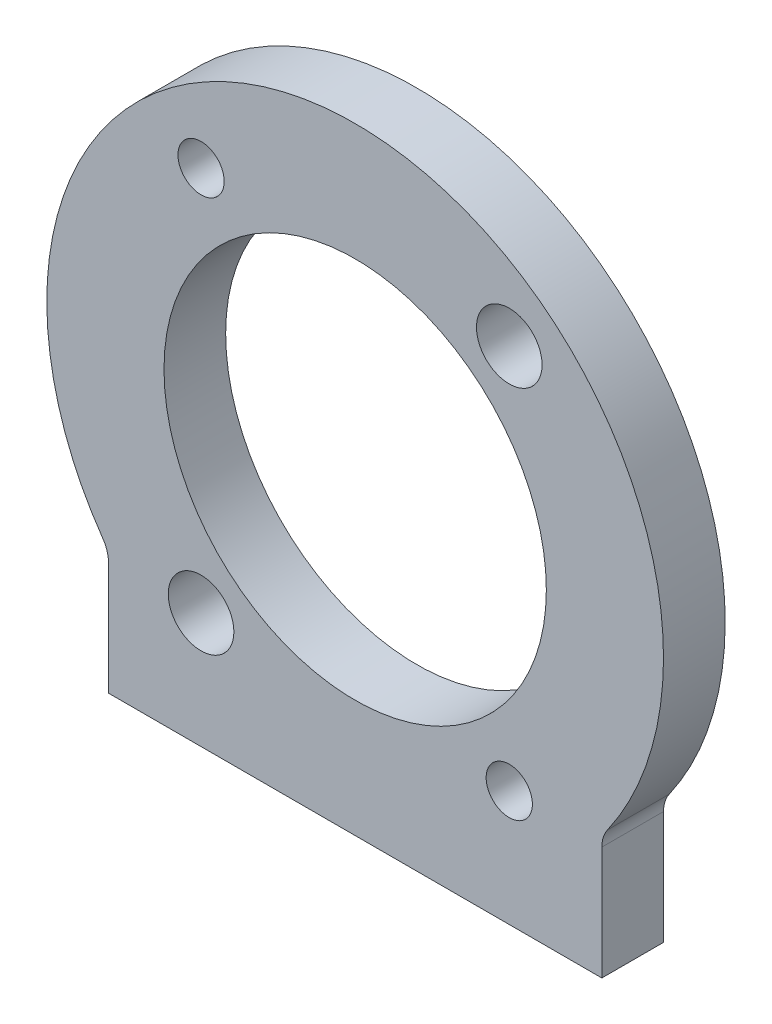
SolidWorks part; units mm, degrees
material "6061 Alloy"
ref_plane "Front" through (0, 0, 0) normal (0, 0, 1) x (1, 0, 0)
ref_plane "Top" through (0, 0, 0) normal (0, 1, 0) x (1, 0, 0)
ref_plane "Right" through (0, 0, 0) normal (1, 0, 0) x (0, 0, -1)
sketch "Sketch1" plane through (0, 0, 0) normal (0, 0, 1) x (1, 0, 0)
  line L0 (-50.8, 63.5) -> (0, 0) construction
  line L1 (0, 0) -> (-50.8, 0)
  line L2 (0, 0) -> (0, 11.6695)
  line L3 (0, 63.5) -> (-50.8, 63.5) construction
  line L4 (-50.8, 0) -> (-50.8, 11.6695)
  line L5 (0, 63.5) -> (-50.8, 0) construction
  line L6 (0, 50.8) -> (0, 63.5) construction
  line L7 (-50.8, 50.8) -> (-50.8, 63.5) construction
  circle A0 centre (-25.4, 31.75) radius 19.685
  circle A2 centre (-25.4, 31.75) radius 25.4 construction
  circle A4 centre (-41.2673, 51.5841) radius 2.3812
  circle A5 centre (-9.5327, 51.5841) radius 3.3782
  circle A6 centre (-9.5327, 11.9159) radius 2.3813
  circle A7 centre (-41.2673, 11.9159) radius 3.3782
  arc A9 (0.5773, 13.495) -> (-51.3773, 13.495) centre (-25.4, 31.75) ccw
  arc A10 (0, 11.6695) -> (0.5773, 13.495) centre (3.175, 11.6695) cw
  arc A11 (-50.8, 11.6695) -> (-51.3773, 13.495) centre (-53.975, 11.6695) ccw
  dimension "D2" = 39.37
  dimension "D4" = 50.8
  dimension "D5" = 4.7625
  dimension "D6" = 6.7564
  dimension "D7" = 31.75
  dimension "D8" = 3.175
  dimension "D1" = 50.8
  dimension "D3" = 31.75
extrude "Boss-Extrude1" add sketch "Sketch1" along normal blind 6.35
